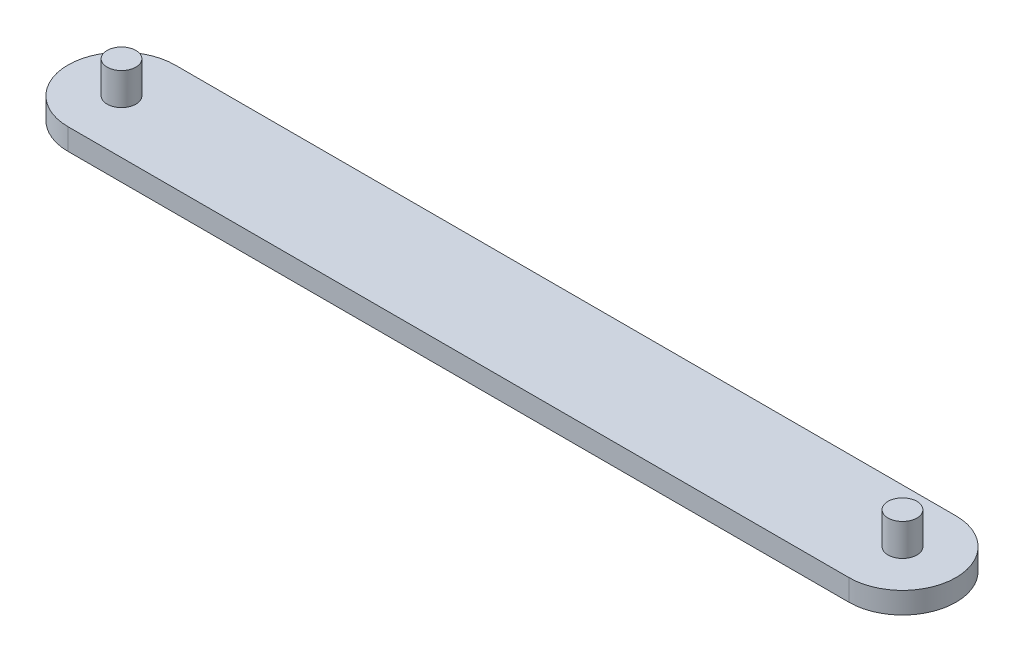
SolidWorks part; units mm, degrees
ref_plane "Front Plane" through (0, 0, 0) normal (0, 0, 1) x (1, 0, 0)
ref_plane "Top Plane" through (0, 0, 0) normal (0, 1, 0) x (1, 0, 0)
ref_plane "Right Plane" through (0, 0, 0) normal (1, 0, 0) x (0, 0, -1)
sketch "Sketch1" plane through (0, 0, 0) normal (0, 1, 0) x (1, 0, 0)
  line L0 (0, 0) -> (-73, 0)
  line L1 (-73, 0) -> (-73, -10) construction
  line L2 (-73, -10) -> (0, -10)
  line L3 (0, -10) -> (0, 0) construction
  arc A0 (0, 0) -> (0, -10) centre (0, -5) cw
  arc A1 (-73, 0) -> (-73, -10) centre (-73, -5) ccw
  dimension "D1" = 73
  dimension "D2" = 10
extrude "Boss-Extrude1" add sketch "Sketch1" along normal blind 2
sketch "Sketch4" plane through (0, 2, 0) normal (0, 1, 0) x (1, 0, 0)
  line L0 (-36.5, 0) -> (-36.5, -10) construction
  line L1 (0, 0) -> (-73, 0) construction
  line L2 (-73, -10) -> (0, -10) construction
  circle A0 centre (-73, -5) radius 1.35
  circle A1 centre (0, -5) radius 1.35
  dimension "D1" = 2.7
extrude "Boss-Extrude2" add sketch "Sketch4" along normal blind 3
